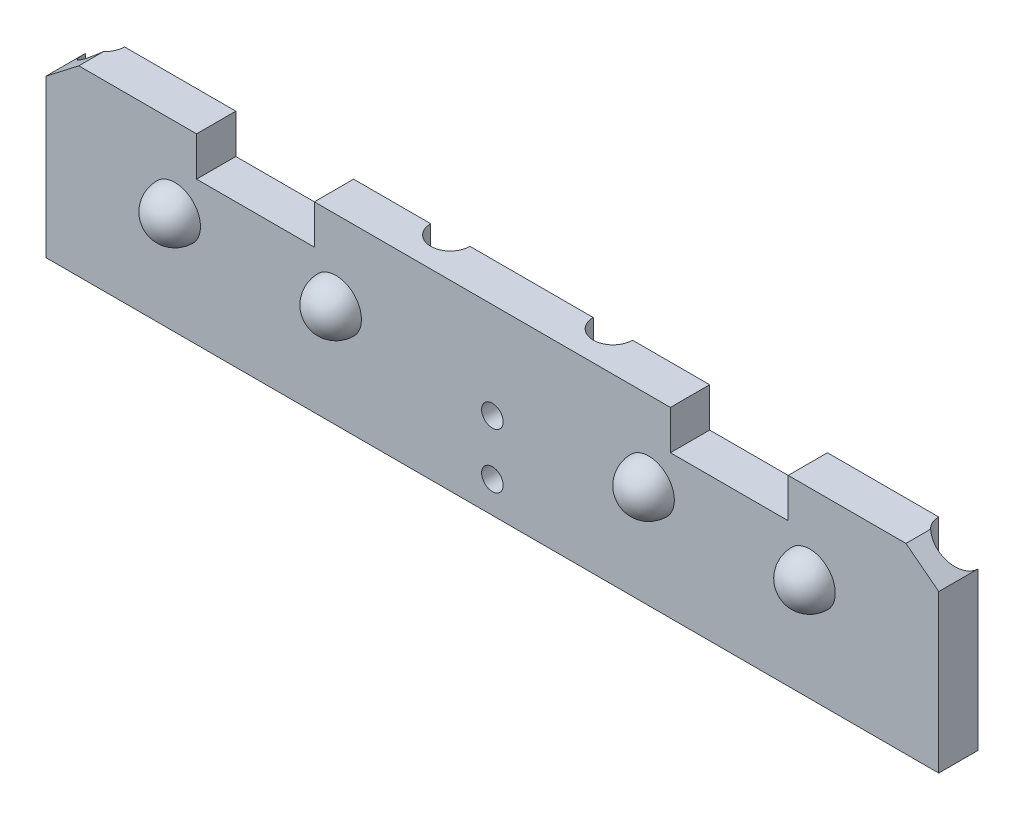
SolidWorks part; units mm, degrees
ref_plane "Front" through (0, 0, 0) normal (0, 0, 1) x (1, 0, 0)
ref_plane "Top" through (0, 0, 0) normal (0, 1, 0) x (1, 0, 0)
ref_plane "Right" through (0, 0, 0) normal (1, 0, 0) x (0, 0, -1)
sketch "Sketch1" plane through (0, 0, 0) normal (0, 0, 1) x (1, 0, 0)
  line L1 (0, 0) -> (126.7, 0)
  line L2 (0, 0) -> (0, 14)
  line L3 (0, 14) -> (126.7, 14)
  line L4 (126.7, 0) -> (126.7, 14)
  dimension "D1" = 126.7
  dimension "D2" = 14
extrude "bracketBase" add sketch "Sketch1" along normal blind 5
sketch "Sketch2" plane through (0, 0, 5) normal (0, 0, 1) x (1, 0, 0)
  line L0 (0, 0) -> (126.7, 0) construction
  line L1 (60.35, 0) -> (66.35, 0) construction
  line L2 (60.35, 0) -> (60.35, 14) construction
  line L3 (60.35, 14) -> (66.35, 14) construction
  line L4 (66.35, 0) -> (66.35, 14) construction
  line L5 (63.35, 0) -> (63.35, -7.3083) construction
  line L7 (120.7, 0) -> (126.7, 0) construction
  line L8 (120.7, 0) -> (120.7, 14) construction
  line L9 (120.7, 14) -> (126.7, 14) construction
  line L10 (126.7, 0) -> (126.7, 14) construction
  circle A0 centre (63.35, 10) radius 1.375
  circle A1 centre (63.35, 3) radius 1.375
  circle A2 centre (123.7, 10) radius 1.375
  circle A3 centre (123.7, 3) radius 1.375
  circle A4 centre (3, 3) radius 1.375
  circle A5 centre (3, 10) radius 1.375
  point P4 (63.35, 0)
  point P7 (63.35, 0)
  point P19 (63.35, 14)
  point P24 (123.7, 14)
  dimension "D3" = 2.75
  dimension "D1" = 14
  dimension "D2" = 6
  dimension "D4" = 4
  dimension "D5" = 7
extrude "mountingHoles" cut sketch "Sketch2" against normal through all both and the other way through all
sketch "distanceSensors" plane through (0, 0, 5) normal (0, 0, 1) x (1, 0, 0)
  line L0 (63.35, 0) -> (63.35, 14) construction
  line L1 (10.675, 2.25) -> (55.675, 2.25) construction
  line L2 (10.675, 2.25) -> (10.675, 22.25) construction
  line L3 (10.675, 22.25) -> (55.675, 22.25) construction
  line L4 (55.675, 2.25) -> (55.675, 22.25) construction
  line L5 (0, 0) -> (126.7, 0) construction
  line L6 (126.7, 14) -> (0, 14) construction
  line L7 (116.025, 2.25) -> (116.025, 22.25) construction
  line L8 (116.025, 2.25) -> (71.025, 2.25) construction
  line L9 (71.025, 2.25) -> (71.025, 22.25) construction
  line L10 (116.025, 22.25) -> (71.025, 22.25) construction
  circle A0 centre (63.35, 3) radius 1.375 construction
  circle A1 centre (63.35, 3) radius 1.375 construction
  circle A2 centre (19.675, 12.25) radius 9 construction
  circle A3 centre (46.675, 12.25) radius 9 construction
  circle A4 centre (80.025, 12.25) radius 9 construction
  circle A5 centre (107.025, 12.25) radius 9 construction
  point P14 (55.675, 12.25)
  dimension "D5" = 18
  dimension "D1" = 20
  dimension "D2" = 45
  dimension "D3" = 7.675
  dimension "D4" = 0.75
  dimension "D6" = 27
sketch "Sketch4" plane through (0, 0, 5) normal (0, 0, 1) x (1, 0, 0)
  line L0 (43.425, 9.0072) -> (43.425, 15.5072)
  arc A0 (43.425, 15.5072) -> (43.425, 9.0072) centre (43.425, 12.2572) ccw
  dimension "D1" = 6.5
  dimension "D2" = 0.0072
  dimension "D3" = 3.25
sketch "Sketch5" plane through (0, 0, 5) normal (0, 0, 1) x (1, 0, 0)
  line L0 (126.7, 0) -> (126.7, 14) construction
  line L1 (0, 14) -> (126.7, 14)
  line L2 (0, 14) -> (0, 22.25)
  line L3 (0, 22.25) -> (126.7, 22.25)
  line L4 (126.7, 14) -> (126.7, 22.25)
  line L5 (116.025, 22.25) -> (71.025, 22.25) construction
extrude "baseExtension" add sketch "Sketch5" against normal up to surface (5 mm away) up to face at (1.625, 3, 0)
sketch "Sketch6" plane through (0, 0, 5) normal (0, 0, 1) x (1, 0, 0)
  line L0 (33.175, 22.25) -> (33.175, 0) construction
  line L1 (10.675, 22.25) -> (55.675, 22.25) construction
  line L2 (0, 0) -> (126.7, 0) construction
  line L3 (43.425, 9.0072) -> (43.425, 15.5072) construction
  line L4 (43.425, 9.0072) -> (43.425, 15.5072) construction
  line L5 (22.925, 9.0072) -> (22.925, 15.5072)
  arc A0 (43.425, 15.5072) -> (43.425, 9.0072) centre (43.425, 12.2572) ccw construction
  arc A1 (43.425, 15.5072) -> (43.425, 9.0072) centre (43.425, 12.2572) ccw construction
  arc A2 (22.925, 15.5072) -> (22.925, 9.0072) centre (22.925, 12.2572) cw
sketch "Sketch7" plane through (0, 0, 5) normal (0, 0, 1) x (1, 0, 0)
  line L0 (43.425, 9.0072) -> (43.425, 15.5072) construction
  line L1 (43.425, 9.0072) -> (43.425, 15.5072) construction
  line L2 (63.35, 0) -> (63.35, 22.25) construction
  line L3 (126.7, 22.25) -> (0, 22.25) construction
  line L4 (83.275, 9.0072) -> (83.275, 15.5072)
  arc A0 (43.425, 15.5072) -> (43.425, 9.0072) centre (43.425, 12.2572) ccw construction
  arc A1 (43.425, 15.5072) -> (43.425, 9.0072) centre (43.425, 12.2572) ccw construction
  arc A2 (83.275, 15.5072) -> (83.275, 9.0072) centre (83.275, 12.2572) cw
sketch "Sketch8" plane through (0, 0, 5) normal (0, 0, 1) x (1, 0, 0)
  line L0 (63.35, 0) -> (63.35, 22.25) construction
  line L1 (0, 0) -> (126.7, 0) construction
  line L2 (22.925, 9.0072) -> (22.925, 15.5072) construction
  line L3 (22.925, 9.0072) -> (22.925, 15.5072) construction
  line L4 (103.775, 9.0072) -> (103.775, 15.5072)
  arc A0 (22.925, 9.0072) -> (22.925, 15.5072) centre (22.925, 12.2572) ccw construction
  arc A1 (22.925, 9.0072) -> (22.925, 15.5072) centre (22.925, 12.2572) ccw construction
  arc A2 (103.775, 9.0072) -> (103.775, 15.5072) centre (103.775, 12.2572) cw
revolve "Revolve1" add sketch "Sketch4" angle 180 about L0
revolve "Revolve2" add sketch "Sketch6" angle 180 about L5 reverse direction yes
revolve "Revolve3" add sketch "Sketch7" angle 180 about L4 reverse direction yes
revolve "Revolve4" add sketch "Sketch8" angle 180 about L4
sketch "Sketch9" plane through (0, 0, 5) normal (0, 0, 1) x (1, 0, 0)
  line L0 (10.675, 22.25) -> (55.675, 22.25) construction
  line L1 (25.675, 22.25) -> (40.675, 22.25)
  line L2 (25.675, 22.25) -> (25.675, 17.25)
  line L3 (25.675, 17.25) -> (40.675, 17.25)
  line L4 (40.675, 22.25) -> (40.675, 17.25)
  line L5 (63.35, 14) -> (63.35, 22.25) construction
  line L6 (126.7, 22.25) -> (0, 22.25) construction
  line L7 (101.025, 17.25) -> (86.025, 17.25)
  line L8 (86.025, 22.25) -> (86.025, 17.25)
  line L9 (101.025, 22.25) -> (86.025, 22.25)
  line L10 (101.025, 22.25) -> (101.025, 17.25)
  point P7 (33.175, 22.25)
  point P8 (33.175, 22.25)
  dimension "D1" = 15
  dimension "D2" = 5
extrude "Cut-Extrude2" cut sketch "Sketch9" against normal through all both and the other way through all
sketch "Sketch10" plane through (0, 0, 5) normal (0, 0, 1) x (1, 0, 0)
  line L0 (116.025, 22.25) -> (126.7, 14)
  line L3 (126.7, 14) -> (126.7, 22.25)
  line L4 (126.7, 22.25) -> (116.025, 22.25)
  line L5 (63.35, 14) -> (63.35, 22.25) construction
  line L6 (86.025, 22.25) -> (40.675, 22.25) construction
  line L7 (0, 14) -> (0, 22.25)
  line L8 (10.675, 22.25) -> (0, 14)
  line L9 (0, 22.25) -> (10.675, 22.25)
extrude "Cut-Extrude3" cut sketch "Sketch10" against normal through all both and the other way through all
sketch "Sketch11" plane through (0, 0, 0) normal (0, -1, 0) x (1, 0, 0)
  line L2 (126.7, 5) -> (126.7, 0) construction
  line L3 (63.35, 0) -> (63.35, 5) construction
  line L4 (0, 0) -> (126.7, 0) construction
  line L5 (0, 5) -> (126.7, 5) construction
  circle A1 centre (126.95, 1.1558) radius 2.5
  circle A2 centre (-0.25, 1.1558) radius 2.5
  dimension "D1" = 5
  dimension "D2" = 0.25
  dimension "D3" = 1.1825
extrude "Cut-Extrude4" cut sketch "Sketch11" against normal through all
sketch "Sketch12" plane through (0, 0, 0) normal (0, -1, 0) x (1, 0, 0)
  line L1 (1.9668, 0) -> (124.7332, 0) construction
  line L2 (63.35, 5) -> (63.35, 0) construction
  line L3 (0, 5) -> (126.7, 5) construction
  circle A0 centre (117.7, 0) radius 2.5
  circle A1 centre (73.7, 0) radius 2.5
  circle A3 centre (53, 0) radius 2.5
  circle A4 centre (9, 0) radius 2.5
  dimension "D1" = 5
  dimension "D2" = 9
  dimension "D3" = 44
extrude "Cut-Extrude5" cut sketch "Sketch12" against normal through all
sketch "Sketch13" plane through (0, 0, 0) normal (0, -1, 0) x (1, 0, 0)
  line L0 (63.35, 5) -> (63.35, 0) construction
  line L1 (0, 5) -> (126.7, 5) construction
  line L2 (55.5, 0) -> (71.2, 0) construction
  line L3 (120.2, 0) -> (124.7332, 0) construction
  line L4 (126.7, 5) -> (120.2, 5)
  line L5 (126.7, 5) -> (126.7, 0)
  line L6 (126.7, 0) -> (120.2, 0)
  line L7 (120.2, 5) -> (120.2, 0)
  line L8 (0, 0) -> (6.5, 0)
  line L9 (6.5, 5) -> (6.5, 0)
  line L10 (0, 5) -> (6.5, 5)
  line L11 (0, 5) -> (0, 0)
  dimension "D1" = 6.5
extrude "Cut-Extrude6" cut sketch "Sketch13" against normal through all both and the other way through all
sketch "Sketch14" plane through (0, 0, 0) normal (0, -1, 0) x (1, 0, 0)
  line L6 (120.2, 0) -> (120.2, 5)
  line L7 (120.2, 5) -> (6.5, 5)
  line L8 (6.5, 5) -> (6.5, 0)
  line L9 (11.5, 0) -> (50.5, 0)
  line L10 (55.5, 0) -> (71.2, 0)
  line L11 (76.2, 0) -> (115.2, 0)
  line L12 (120.2, 0) -> (120.2, 5)
  line L13 (120.2, 5) -> (6.5, 5)
  line L14 (6.5, 5) -> (6.5, 0)
  line L15 (11.5, 0) -> (50.5, 0)
  line L16 (55.5, 0) -> (71.2, 0)
  line L17 (76.2, 0) -> (115.2, 0)
  arc A4 (120.2, 0) -> (115.2, 0) centre (117.7, 0) ccw
  arc A5 (11.5, 0) -> (6.5, 0) centre (9, 0) ccw
  arc A6 (55.5, 0) -> (50.5, 0) centre (53, 0) ccw
  arc A7 (76.2, 0) -> (71.2, 0) centre (73.7, 0) ccw
  arc A8 (120.2, 0) -> (115.2, 0) centre (117.7, 0) ccw
  arc A9 (11.5, 0) -> (6.5, 0) centre (9, 0) ccw
  arc A10 (55.5, 0) -> (50.5, 0) centre (53, 0) ccw
  arc A11 (76.2, 0) -> (71.2, 0) centre (73.7, 0) ccw
  dimension "D1" = 0
extrude "Boss-Extrude1" add sketch "Sketch14" along normal blind 1
